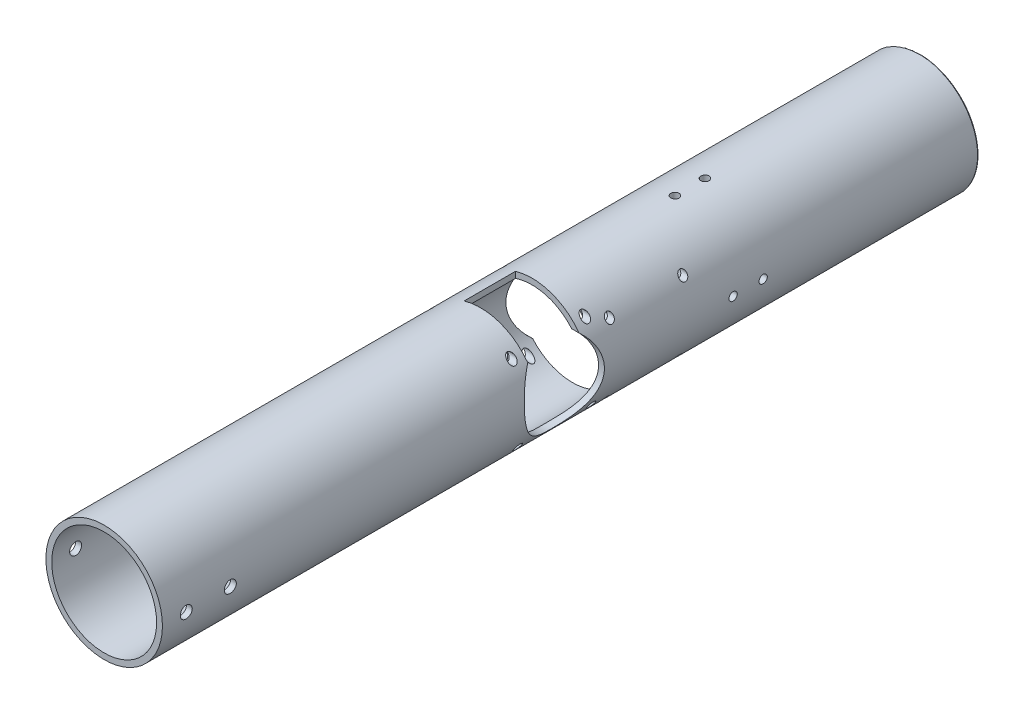
SolidWorks part; units mm, degrees
material "6061 Alloy"
ref_plane "Front Plane" through (0, 0, 0) normal (0, 0, 1) x (1, 0, 0)
ref_plane "Top Plane" through (0, 0, 0) normal (0, 1, 0) x (1, 0, 0)
ref_plane "Right Plane" through (0, 0, 0) normal (1, 0, 0) x (0, 0, -1)
sketch "Sketch1" plane through (0, 0, 0) normal (0, 0, 1) x (1, 0, 0)
  circle A0 centre (0, 0) radius 31.75
  circle A1 centre (0, 0) radius 28.575
  dimension "D1" = 63.5
  dimension "D2" = 57.15
extrude "Boss-Extrude1" add sketch "Sketch1" along normal blind 125 and the other way blind 250 contours A1 | A0
sketch "Sketch2" plane through (0, 0, 0) normal (1, 0, 0) x (0, 0, -1)
  circle A2 centre (73.488, -2) radius 21.75
  dimension "D1" = 43.5
  dimension "D2" = 73.488
  dimension "D3" = 2
extrude "Cut-Extrude1" cut sketch "Sketch2" against normal through all
sketch "Sketch3" plane through (0, 0, 0) normal (1, 0, 0) x (0, 0, -1)
  circle A1 centre (23.45, 2) radius 21.75
  dimension "D1" = 23.45
  dimension "D2" = 43.5
  dimension "D3" = 2
extrude "Cut-Extrude2" cut sketch "Sketch3" along normal through all
sketch "Sketch5" plane through (0, 0, 0) normal (1, 0, 0) x (0, 0, -1)
  line L1 (87.488, -12.75) -> (59.488, -12.75)
  line L2 (87.488, -12.75) -> (87.488, -34.75)
  line L3 (87.488, -34.75) -> (59.488, -34.75)
  line L4 (59.488, -12.75) -> (59.488, -34.75)
  line L5 (87.488, -12.75) -> (59.488, -34.75) construction
  line L6 (87.488, -34.75) -> (59.488, -12.75) construction
  circle A0 centre (73.488, -2) radius 21.75 construction
  circle A1 centre (73.488, -2) radius 21.75 construction
  circle A2 centre (73.488, -2) radius 21.75 construction
  point P0 (73.488, -23.75)
  dimension "D1" = 28
  dimension "D2" = 22
extrude "Cut-Extrude4" cut sketch "Sketch5" against normal through all from offset 9
sketch "Sketch6" plane through (0, 0, 0) normal (1, 0, 0) x (0, 0, -1)
  line L1 (9.45, 34.75) -> (37.45, 34.75)
  line L2 (9.45, 34.75) -> (9.45, 12.75)
  line L3 (9.45, 12.75) -> (37.45, 12.75)
  line L4 (37.45, 34.75) -> (37.45, 12.75)
  line L5 (9.45, 34.75) -> (37.45, 12.75) construction
  line L6 (9.45, 12.75) -> (37.45, 34.75) construction
  circle A0 centre (23.45, 2) radius 21.75 construction
  circle A1 centre (23.45, 2) radius 21.75 construction
  circle A2 centre (23.45, 2) radius 21.75 construction
  point P0 (23.45, 23.75)
  dimension "D1" = 28
  dimension "D2" = 22
extrude "Cut-Extrude5" cut sketch "Sketch6" along normal through all from offset 9 offset against normal yes
sketch "Sketch10" plane through (0, 0, 0) normal (1, 0, 0) x (0, 0, -1)
  line L1 (113.488, 38) -> (33.488, 38)
  line L2 (113.488, 38) -> (113.488, -42)
  line L3 (113.488, -42) -> (33.488, -42)
  line L4 (33.488, 38) -> (33.488, -42)
  line L5 (113.488, 38) -> (33.488, -42) construction
  line L6 (113.488, -42) -> (33.488, 38) construction
  point P0 (73.488, -2)
  dimension "D1" = 80
  dimension "D2" = 80
sketch "Sketch11" plane through (0, 0, 0) normal (1, 0, 0) x (0, 0, -1)
  line L0 (113.488, 38) -> (33.488, -42) construction
  line L1 (113.488, -42) -> (33.488, 38) construction
  line L2 (51.738, -2) -> (95.238, -2) construction
  line L3 (53.488, 18) -> (53.488, -22) construction
  circle A0 centre (93.488, 18) radius 2
  circle A1 centre (53.488, 18) radius 2
  circle A2 centre (53.488, -22) radius 2
  circle A3 centre (93.488, -22) radius 2
  arc A4 (87.488, -18.6452) -> (59.488, -18.6452) centre (73.488, -2) ccw construction
  arc A5 (87.488, -18.6452) -> (59.488, -18.6452) centre (73.488, -2) ccw construction
  point P18 (53.488, -2)
  dimension "D5" = 4
  dimension "D1" = 40
extrude "Cut-Extrude8" cut sketch "Sketch11" against normal through all both and the other way through all
sketch "Sketch12" plane through (0, 0, 0) normal (1, 0, 0) x (0, 0, -1)
  line L0 (-125, 31.75) -> (-125, -31.75) construction
  circle A0 centre (-112, 0) radius 3.25
  circle A1 centre (-88, 0) radius 3.25
  dimension "D2" = 6.5
  dimension "D3" = 24
  dimension "D4" = 13
extrude "Cut-Extrude10" cut sketch "Sketch12" against normal through all both and the other way through all
sketch "Sketch13" plane through (0, 0, 0) normal (0, 1, 0) x (1, 0, 0)
  line L0 (0, -34.925) -> (0, 34.925) construction
  line L1 (28.575, 250) -> (-28.575, 250) construction
  line L2 (0, 250) -> (0, -125) construction
  circle A0 centre (0, 238) radius 2.25 construction
  circle A1 centre (0, 205.9) radius 2.25 construction
  dimension "D2" = 4.5
  dimension "D3" = 32.1
  dimension "D1" = 12
sketch "Sketch14" plane through (0, 0, 0) normal (1, 0, 0) x (0, 0, -1)
  line L0 (3.45, -18) -> (3.45, 22) construction
  line L1 (-1.55, 27) -> (48.45, 27) construction
  line L2 (-1.55, 27) -> (-1.55, -23) construction
  line L3 (-1.55, -23) -> (48.45, -23) construction
  line L4 (48.45, 27) -> (48.45, -23) construction
  line L5 (-1.55, 27) -> (48.45, -23) construction
  line L6 (-1.55, -23) -> (48.45, 27) construction
  circle A0 centre (3.45, 22) radius 2
  circle A1 centre (43.45, 22) radius 2
  circle A2 centre (43.45, -18) radius 2
  circle A3 centre (3.45, -18) radius 2
  point P0 (23.45, 2)
  point P14 (3.45, 2)
  dimension "D5" = 4
  dimension "D1" = 40
  dimension "D2" = 50
sketch "Sketch15" plane through (0, 0, 0) normal (1, 0, 0) x (0, 0, -1)
  circle A0 centre (3.45, 22) radius 2
  circle A1 centre (43.45, 22) radius 2
  circle A2 centre (43.45, -18) radius 2
  circle A3 centre (3.45, -18) radius 2
  dimension "D1" = 4
extrude "Cut-Extrude12" cut sketch "Sketch15" against normal through all and the other way through all
hole_wizard "M4 Clearance Hole1" positions "Sketch18" profile "Sketch19" hole size "M4" standard "ANSI Metric"
sketch "Sketch18" plane through (0, 0, 0) normal (1, 0, 0) x (0, 0, -1)
  circle A0 centre (3.45, 22) radius 2 construction
  circle A1 centre (43.45, 22) radius 2 construction
  circle A2 centre (3.45, -18) radius 2 construction
  circle A3 centre (43.45, -18) radius 2 construction
  point P0 (3.45, 22)
  point P2 (43.45, 22)
  point P4 (3.45, -18)
  point P6 (43.45, -18)
  point P20 (93.488, 18)
  point P23 (53.488, 18)
  point P26 (93.488, -22)
  point P29 (53.488, -22)
sketch "Sketch19" plane through (0, 22, -3.45) normal (0, 1, 0) x (0, 0, 1)
  line L0 (0, 0) -> (0, 31.75)
  line L1 (0, 31.75) -> (2.25, 31.75)
  line L2 (2.25, 31.75) -> (2.25, 0)
  line L5 (2.25, 0) -> (0, 0)
  line L11 (0, -6.35) -> (0, 107.95) construction
  dimension "Thru Hole Dia." = 4.5
  dimension "Thru Hole Depth" = 31.75
mirror "Mirror1" about plane through (0, 0, 0) normal (1, 0, 0) of "M4 Clearance Hole1"
sketch "Sketch21" plane through (0, 0, -250) normal (0, 0, -1) x (-1, 0, 0)
  circle A0 centre (0, 0) radius 30
  dimension "D1" = 60
extrude "Cut-Extrude14" cut sketch "Sketch21" against normal blind 7
sketch "Sketch22" plane through (0, 0, 0) normal (1, 0, 0) x (0, 0, -1)
  line L0 (250, -31.75) -> (250, 31.75) construction
  line L1 (250, -31.75) -> (250, 31.75) construction
  circle A0 centre (221.65, 0) radius 2.25 construction
  circle A1 centre (131.65, 0) radius 2.25
  circle A2 centre (115.3, 0) radius 2.25
  circle A4 centre (238, 0) radius 2.25 construction
  point P14 (250, 0)
  dimension "D1" = 134.7
  dimension "D4" = 12
  dimension "D5" = 4.5
  dimension "D2" = 118.35
  dimension "D3" = 28.35
extrude "Cut-Extrude15" cut sketch "Sketch22" along normal through all
pattern_circular "CirPattern2" count 4 over 360 about axis through (0, 0, -250) along (0, 0, 1) of "Cut-Extrude15"
sketch "Sketch23" plane through (0, 0, -243) normal (0, 0, -1) x (-1, 0, 0)
  circle A0 centre (0, 0) radius 28.575 construction
  circle A1 centre (0, 0) radius 30
  circle A2 centre (0, 0) radius 30
  circle A3 centre (0, 0) radius 28.575
  dimension "D1" = 0
extrude "Boss-Extrude2" add sketch "Sketch23" along normal up to surface (7 mm away) up to face at (-30, 0, -250)
ref_plane "Plane1" through (0, 0, 75) normal (0, 0, 1) x (1, 0, 0)
split "Split1" trim tools "Plane1" bodies to split 124 resulting bodies 125 126
move or copy body "Body-Move/Copy1" bodies to move or copy 125 copy no translate (0, 0, 70.65) parameters "D1"=0, "D2"=0, "D3"=70.65
sketch "Sketch24" plane through (0, 0, 75) normal (0, 0, 1) x (1, 0, 0)
  circle A0 centre (0, 0) radius 28.575 construction
  circle A1 centre (0, 0) radius 31.75
  circle A2 centre (0, 0) radius 31.75
  circle A3 centre (0, 0) radius 28.575
  dimension "D1" = 0
extrude "Boss-Extrude3" add sketch "Sketch24" along normal up to surface (70.65 mm away) up to face at (31.75, 0, 145.65)
sketch "Sketch25" plane through (0, 0, -250) normal (0, 0, -1) x (-1, 0, 0)
  circle A0 centre (0, 0) radius 31.75 construction
  circle A1 centre (0, 0) radius 31.75
extrude "Cut-Extrude16" cut sketch "Sketch25" against normal blind 1
fillet "Fillet1" radius 0.5 2 edges at (-28.575, 0, -249) (-31.75, 0, -249)
